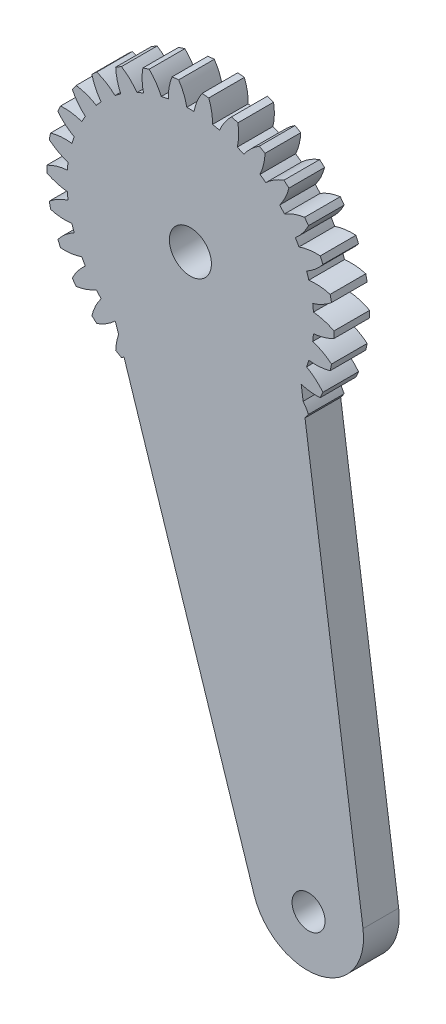
SolidWorks part; units mm, degrees
ref_plane "Front Plane" through (0, 0, 0) normal (0, 0, 1) x (1, 0, 0)
ref_plane "Top Plane" through (0, 0, 0) normal (0, 1, 0) x (1, 0, 0)
ref_plane "Right Plane" through (0, 0, 0) normal (1, 0, 0) x (0, 0, -1)
sketch "Sketch1" plane through (0, 0, 0) normal (0, 0, 1) x (1, 0, 0)
  circle A0 centre (0, 0) radius 12.8
  dimension "D1" = 25.6
extrude "Boss-Extrude1" add sketch "Sketch1" along normal blind 3.18
sketch "Sketch2" plane through (0, 0, 3.18) normal (0, 0, 1) x (1, 0, 0)
  line L0 (0, 0) -> (0, 12.8) construction
  line L1 (0, 0) -> (-1.338, 12.7299) construction
  line L2 (-0.6243, 11.9838) -> (-1.2526, 11.9177) construction
  circle A0 centre (0, 0) radius 11 construction
  circle A1 centre (0, 0) radius 11.2763 construction
  circle A2 centre (0, 0) radius 12 construction
  circle A5 centre (0, 0) radius 12.8 construction
  arc A6 (-0.321, 10.9953) -> (0.321, 10.9953) centre (0, 0) cw
  arc A7 (-1.0443, 12.7573) -> (1.0443, 12.7573) centre (0, 0) cw
  arc A8 (-1.0443, 12.7573) -> (-0.321, 10.9953) centre (-5.0349, 10.0899) cw
  arc A9 (0.321, 10.9953) -> (1.0443, 12.7573) centre (5.0349, 10.0899) cw
  dimension "D1" = 22
  dimension "D2" = 22.5526
  dimension "D3" = 24
  dimension "D5" = 4.8
  dimension "D6" = 4.8
  dimension "D4" = 6
  dimension "D7" = 0.6283
extrude "Cut-Extrude1" cut sketch "Sketch2" against normal through all
pattern_circular "CirPattern1" count 30 over 360 about axis through (0, 0, 3.18) along (0, 0, 1) of face at (-0.6385, 11.8944, 1.59) of face at (0, 10.9977, 1.59) of face at (0.6385, 11.8944, 1.59)
ref_axis "Axis1" through (0, 0, 0) along (0, 0, 1)
sketch "Sketch4" plane through (0, 0, 0) normal (0, 0, -1) x (-1, 0, 0)
  circle A0 centre (0, 0) radius 1.875
  dimension "D1" = 3.75
extrude "Cut-Extrude3" cut sketch "Sketch4" against normal through all
sketch "Sketch6" plane through (0, 0, 0) normal (0, 0, -1) x (-1, 0, 0)
  line L0 (-9.8286, -4.9395) -> (-15.3863, -44.5515)
  line L1 (6.6727, -8.745) -> (-5.6792, -46.7902)
  line L2 (0, 0) -> (-10.4348, -45.2462) construction
  line L5 (0, 0) -> (0, 7.6918) construction
  arc A0 (-9.8286, -4.9395) -> (6.6727, -8.745) centre (0, 0) ccw
  arc A7 (-15.3863, -44.5515) -> (-5.6792, -46.7902) centre (-10.4348, -45.2462) ccw
  arc A8 (-6.7226, -8.7067) -> (-6.2032, -9.0841) centre (0, 0) ccw construction
  dimension "D1" = 5
  dimension "D4" = 167.013
  dimension "D2" = 10
  dimension "D3" = 40
extrude "Boss-Extrude2" add sketch "Sketch6" against normal blind 3.18
sketch "Sketch7" plane through (0, 0, 3.18) normal (0, 0, 1) x (1, 0, 0)
  line L0 (5.6792, -46.7902) -> (15.3863, -44.5515) construction
  circle A2 centre (10.5327, -45.6708) radius 1.47
  dimension "D1" = 2.94
extrude "Cut-Extrude4" cut sketch "Sketch7" against normal through all
equation "\"module\"= .8"
equation "\"teeth\"= 30"
equation "\"pressureAngle\"= 20deg"
equation "\"gearThickness\"=3.18"
equation "\"addendumFactor\"= 1"
equation "\"dedendumFactor\"= 1.25"
equation "\"pitch\"= 1 / \"module\""
equation "\"pitchDiameter\"= \"teeth\" / \"pitch\""
equation "\"addendum\"= \"addendumFactor\" / \"pitch\""
equation "\"dedendum\"= \"dedendumFactor\" / \"pitch\""
equation "\"D1@Sketch1\"=\"pitchDiameter\" + 2 * \"addendum\""
equation "\"D1@Boss-Extrude1\"=\"gearThickness\""
equation "\"D1@Sketch2\"=\"pitchDiameter\" - 2 * \"dedendum\""
equation "\"D2@Sketch2\"=\"pitchDiameter\" * cos(\"pressureAngle\")"
equation "\"D3@Sketch2\"=\"pitchDiameter\""
equation "\"D4@Sketch2\"=180/\"teeth\""
equation "\"D5@Sketch2\"=\"pitchDiameter\"/5"
equation "\"D6@Sketch2\"=\"pitchDiameter\"/5"
equation "\"D7@Sketch2\"= PI / 2 / \"pitch\"/2"
equation "\"D1@CirPattern1\"=\"teeth\""
